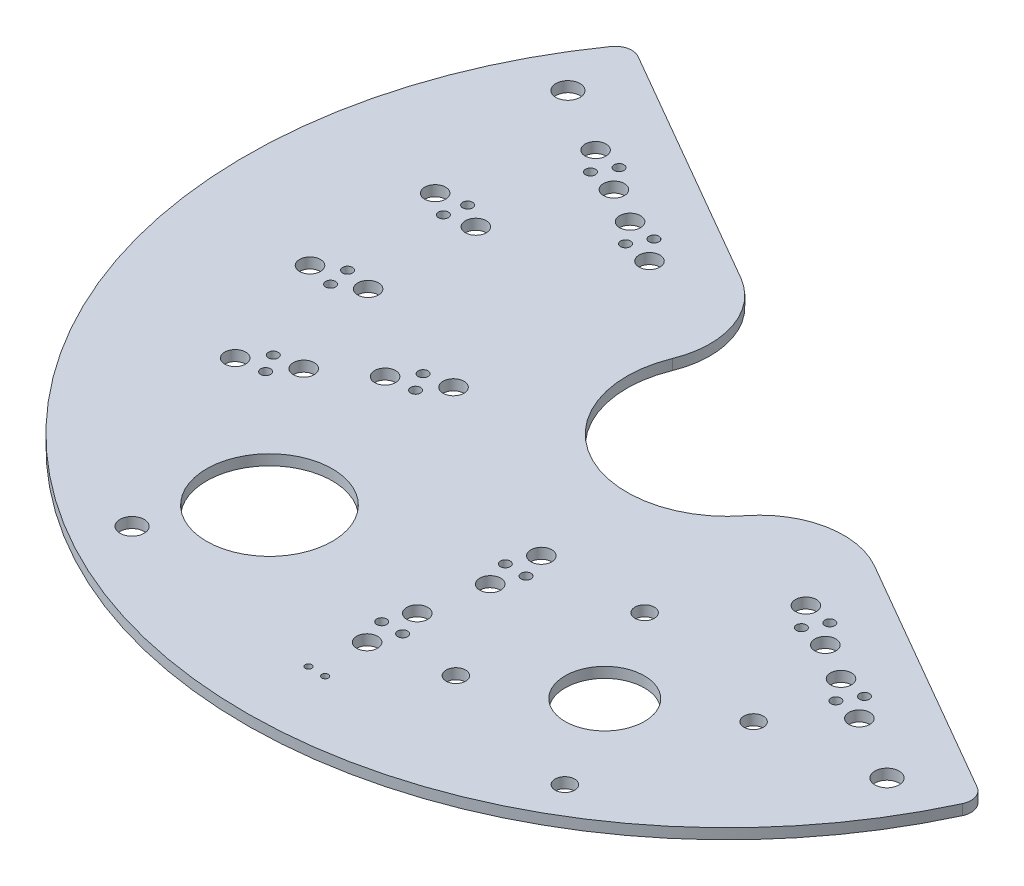
SolidWorks part; units mm, degrees
ref_plane "Front Plane" through (0, 0, 0) normal (0, 0, 1) x (1, 0, 0)
ref_plane "Top Plane" through (0, 0, 0) normal (0, 1, 0) x (1, 0, 0)
ref_plane "Right Plane" through (0, 0, 0) normal (1, 0, 0) x (0, 0, -1)
sketch "Sketch1" plane through (0, 0, 0) normal (0, 1, 0) x (1, 0, 0)
  line L0 (0, 50.8) -> (0, 59.6199) construction
  line L1 (0, 50.8) -> (11.3081, 50.8) construction
  line L2 (0, 0) -> (0, 47) construction
  line L3 (0, 0) -> (-46.286, 8.1615) construction
  line L4 (0, 0) -> (0, 47) construction
  line L5 (0, 0) -> (-46.286, -8.1615) construction
  line L6 (-30.1951, -16.4814) -> (-38.7564, -18.616) construction
  line L7 (1.7716, -33.8648) -> (4.3514, -25.4269) construction
  line L8 (31.2901, -20.38) -> (25.051, -14.141) construction
  line L9 (-31.8057, 17.1605) -> (-38.0448, 23.3996) construction
  circle A0 centre (0, 0) radius 50.8 construction
  circle A1 centre (0, 0) radius 15.24
  circle A2 centre (0, 0) radius 73.025
  circle A3 centre (0, 50.8) radius 6.3 construction
  circle A4 centre (25.4, 43.9941) radius 6.3 construction
  circle A5 centre (43.9941, 25.4) radius 6.3 construction
  circle A6 centre (50.8, 0) radius 6.3 construction
  circle A7 centre (43.9941, -25.4) radius 6.3 construction
  circle A8 centre (25.4, -43.9941) radius 6.3 construction
  circle A9 centre (0, -50.8) radius 6.3 construction
  circle A10 centre (-25.4, -43.9941) radius 6.3 construction
  circle A11 centre (-43.9941, -25.4) radius 6.3 construction
  circle A12 centre (-50.8, 0) radius 6.3 construction
  circle A13 centre (-43.9941, 25.4) radius 6.3 construction
  circle A14 centre (-25.4, 43.9941) radius 6.3 construction
  circle A15 centre (0, 50.8) radius 1.585 construction
  circle A16 centre (-1.585, 50.8) radius 0.75
  circle A17 centre (1.585, 50.8) radius 0.75
  circle A18 centre (0, 50.8) radius 3.8 construction
  circle A19 centre (0, 54.6) radius 1.585
  circle A20 centre (0, 47) radius 1.585
  circle A21 centre (47.285, 27.3) radius 1.585
  circle A22 centre (43.2016, 26.7727) radius 0.75
  circle A23 centre (44.7866, 24.0273) radius 0.75
  circle A24 centre (40.7032, 23.5) radius 1.585
  circle A25 centre (47.285, -27.3) radius 1.585
  circle A26 centre (44.7866, -24.0273) radius 0.75
  circle A27 centre (43.2016, -26.7727) radius 0.75
  circle A28 centre (40.7032, -23.5) radius 1.585
  circle A29 centre (0, -54.6) radius 1.585
  circle A30 centre (1.585, -50.8) radius 0.75
  circle A31 centre (-1.585, -50.8) radius 0.75
  circle A32 centre (0, -47) radius 1.585
  circle A33 centre (-47.285, -27.3) radius 1.585
  circle A34 centre (-43.2016, -26.7727) radius 0.75
  circle A35 centre (-44.7866, -24.0273) radius 0.75
  circle A36 centre (-40.7032, -23.5) radius 1.585
  circle A37 centre (-47.285, 27.3) radius 1.585
  circle A38 centre (-44.7866, 24.0273) radius 0.75
  circle A39 centre (-43.2016, 26.7727) radius 0.75
  circle A40 centre (-40.7032, 23.5) radius 1.585
  circle A41 centre (25.4, 43.9941) radius 20
  circle A42 centre (-25.4, -43.9941) radius 9.525
  circle A43 centre (25.4, -43.9941) radius 6
  circle A44 centre (-46.286, 8.1615) radius 1.585
  circle A45 centre (-50.3035, 7.2604) radius 0.75
  circle A46 centre (-49.753, 10.3822) radius 0.75
  circle A47 centre (-53.7705, 9.4812) radius 1.585
  circle A48 centre (-46.286, -8.1615) radius 1.585
  circle A49 centre (-49.753, -10.3822) radius 0.75
  circle A50 centre (-50.3035, -7.2604) radius 0.75
  circle A51 centre (-53.7705, -9.4812) radius 1.585
  circle A52 centre (-30.191, -16.4817) radius 6.3 construction
  circle A53 centre (-30.191, -16.4817) radius 1.585 construction
  circle A54 centre (-29.3973, -17.8553) radius 0.75
  circle A55 centre (-31.002, -15.1168) radius 0.75
  circle A56 centre (-30.191, -16.4817) radius 3.8 construction
  circle A57 centre (-33.5032, -18.378) radius 1.585
  circle A58 centre (-26.9143, -14.5903) radius 1.585
  circle A59 centre (1.7693, -33.8681) radius 6.3 construction
  circle A60 centre (1.7693, -33.8681) radius 1.585 construction
  circle A61 centre (0.1831, -33.841) radius 0.75
  circle A62 centre (3.3569, -33.8759) radius 0.75
  circle A63 centre (1.7693, -33.8681) radius 3.8 construction
  circle A64 centre (1.8498, -30.0524) radius 1.585
  circle A65 centre (1.7028, -37.651) radius 1.585
  circle A66 centre (31.7545, -18.4007) radius 6.3 construction
  circle A67 centre (31.7545, -18.4007) radius 1.585 construction
  circle A68 centre (30.9859, -19.7885) radius 0.75
  circle A69 centre (32.5067, -17.0026) radius 0.75
  circle A70 centre (31.7545, -18.4007) radius 3.8 construction
  circle A71 centre (28.4231, -16.5382) radius 1.585
  circle A72 centre (35.0633, -20.2353) radius 1.585
  circle A73 centre (-31.9359, 18.6471) radius 6.3 construction
  circle A74 centre (-31.9359, 18.6471) radius 1.585 construction
  circle A75 centre (-32.7045, 17.2593) radius 0.75
  circle A76 centre (-31.1837, 20.0452) radius 0.75
  circle A77 centre (-31.9359, 18.6471) radius 3.8 construction
  circle A78 centre (-35.2672, 20.5095) radius 1.585
  circle A79 centre (-28.627, 16.8125) radius 1.585
  point P50 (0, 0)
  point P84 (0, 0)
  dimension "D1" = 12
  dimension "D2" = 101.6
  dimension "D3" = 3.17
  dimension "D4" = 1.5
  dimension "D5" = 7.6
  dimension "D6" = 6
  dimension "D7" = 3.17
  dimension "D8" = 40
  dimension "D9" = 19.05
  dimension "D10" = 12
  dimension "D11" = 146.05
  dimension "D12" = 30.48
  dimension "D14" = 80
  dimension "D16" = 100
  dimension "D13" = 2
  dimension "D15" = 2
extrude "Boss-Extrude1" add sketch "Sketch1" against normal blind 1.5875
sketch "Sketch2" plane through (0, 0, 0) normal (0, 1, 0) x (1, 0, 0)
  line L0 (0, 0) -> (0, 66.04) construction
  line L1 (0, 0) -> (-57.1923, 33.02) construction
  circle A0 centre (0, 0) radius 66.04 construction
  circle A1 centre (0, 66.04) radius 1.8288 construction
  circle A2 centre (-57.1923, 33.02) radius 1.8288
  circle A3 centre (33.02, 57.1923) radius 1.8288
  circle A4 centre (57.1923, -33.02) radius 1.8288
  circle A5 centre (-33.02, -57.1923) radius 1.8288
  point P17 (0, 0)
  dimension "D1" = 132.08
  dimension "D2" = 3.6576
  dimension "D3" = 2
  dimension "D4" = 60
  dimension "D5" = 4
extrude "Cut-Extrude1" cut sketch "Sketch2" against normal through all
sketch "Sketch3" plane through (0, 0, 0) normal (0, 1, 0) x (1, 0, 0)
  line L0 (-57.1923, 33.02) -> (57.1923, -33.02) construction
  line L1 (-59.5338, 44.6372) -> (68.4238, -29.2392)
  line L2 (-52.7473, 40.719) -> (61.6373, -25.321) construction
  arc A0 (68.4238, -29.2392) -> (-59.5338, 44.6372) centre (0, 0) ccw
  dimension "D1" = 8.89
extrude "Cut-Extrude2" cut sketch "Sketch3" against normal through all
fillet "Fillet1" radius 12.7 2 edges at (15.165, -0.7937, -1.5098) (-6.275, -0.7937, -13.8882)
fillet "Fillet2" radius 2.54 2 edges at (67.2161, -0.7937, 28.542) (-58.3261, -0.7937, -43.9399)
sketch "Sketch4" plane through (0, 0, 0) normal (0, 1, 0) x (1, 0, 0)
  line L0 (0, 0) -> (0, -73.025) construction
  arc A0 (-59.6949, 42.0615) -> (66.2738, -30.6666) centre (0, 0) ccw construction
  circle A1 centre (0, 0) radius 62.23 construction
  circle A2 centre (0, -62.23) radius 0.4953 construction
  circle A3 centre (1.27, -62.23) radius 0.4953
  circle A4 centre (-1.27, -62.23) radius 0.4953
  dimension "D1" = 0.9906
  dimension "D4" = 124.46
  dimension "D2" = 2
  dimension "D3" = 2
extrude "Cut-Extrude3" cut sketch "Sketch4" against normal through all
sketch "Sketch5" plane through (0, -1.5875, 0) normal (0, -1, 0) x (1, 0, 0)
  line L0 (34.4907, 15.2341) -> (45.0238, 21.3018)
  line L1 (-31.0536, -21.3854) -> (-30.5378, -22.2779)
  line L2 (-30.0652, -20.8147) -> (-29.5513, -21.704)
  line L3 (-30.5378, -22.2779) -> (-40.9598, -28.3409)
  line L13 (33.3365, 26.1699) -> (41.5359, 31.0198)
  line L14 (28.0125, 9.134) -> (57.7422, 26.2984)
  line L29 (46.7892, 22.3211) -> (54.7743, 26.9312)
  line L30 (29.0711, 12.1121) -> (33.5009, 14.6639)
  line L31 (6.096, 41.9407) -> (6.096, 51.4811)
  line L32 (32.4795, 23.822) -> (40.9598, 28.3409)
  line L33 (-6.096, 38.6381) -> (-6.096, 51.4811)
  line L34 (4.064, 40.0736) -> (4.064, 49.6426)
  line L35 (-21.9165, -19.6925) -> (-41.5359, -31.0198)
  line L39 (-4.064, 36.8606) -> (-4.064, 49.6426)
  line L40 (-30.4135, 24.5983) -> (-41.5359, 31.0198)
  line L42 (-29.8903, 21.9498) -> (-40.9598, 28.3409)
  line L93 (-25.0455, -19.0828) -> (-29.5513, -21.704)
  arc A0 (1.2946, 63.4357) -> (1.2454, 61.0243) centre (1.27, 62.23) ccw
  arc A1 (-1.1373, 61.0264) -> (-1.1844, 63.4379) centre (-1.27, 62.23) ccw
  arc A2 (-1.1373, 61.0264) -> (-54.0489, -28.3589) centre (0, 0) ccw
  arc A3 (-1.1844, 63.4379) -> (-56.1144, -29.6131) centre (0, 0) ccw
  arc A4 (54.7743, 26.9312) -> (1.2454, 61.0243) centre (0, 0) ccw
  arc A5 (-56.1144, -29.6131) -> (-54.0489, -28.3589) centre (-55.1689, -28.8424) ccw
  arc A6 (6.096, 51.4811) -> (2.3857, 51.7858) centre (0, 0) ccw
  arc A7 (32.4795, 23.822) -> (4.064, 40.0736) centre (0, 0) ccw
  arc A8 (2.3857, 51.7858) -> (2.3071, 49.7553) centre (1.585, 50.8) ccw
  arc A9 (-2.3071, 49.7553) -> (-2.3857, 51.7858) centre (-1.585, 50.8) ccw
  arc A10 (-48.5987, -10.912) -> (-50.5848, -11.342) centre (-49.753, -10.3822) ccw
  arc A11 (-51.4133, -6.6431) -> (-49.4, -6.3679) centre (-50.3035, -7.2604) ccw
  arc A12 (46.0407, 23.8268) -> (44.2429, 22.8796) centre (44.7866, 24.0273) ccw
  arc A13 (41.9358, 26.8756) -> (43.655, 27.959) centre (43.2016, 26.7727) ccw
  arc A14 (-49.4, 6.3679) -> (-51.4133, 6.6431) centre (-50.3035, 7.2604) ccw
  arc A15 (-50.5848, 11.342) -> (-48.5987, 10.912) centre (-49.753, 10.3822) ccw
  arc A16 (57.7422, 26.2984) -> (1.2946, 63.4357) centre (0, 0) ccw
  arc A17 (-2.3857, 51.7858) -> (-6.096, 51.4811) centre (0, 0) ccw
  arc A18 (-2.3071, 49.7553) -> (-4.064, 49.6426) centre (0, 0) ccw
  arc A19 (45.0238, 21.3018) -> (44.2429, 22.8796) centre (0, 0) ccw
  arc A20 (29.0711, 12.1121) -> (-25.0455, -19.0828) centre (2.3366, -4.0471) ccw
  arc A21 (28.0125, 9.134) -> (-21.9165, -19.6925) centre (2.3859, -4.1326) ccw
  arc A22 (46.7892, 22.3211) -> (46.0407, 23.8268) centre (0, 0) ccw
  arc A23 (43.655, 27.959) -> (41.5359, 31.0198) centre (0, 0) ccw
  arc A24 (-46.0407, -23.8268) -> (-44.2429, -22.8796) centre (-44.7866, -24.0273) ccw
  arc A25 (-41.9358, -26.8756) -> (-43.655, -27.959) centre (-43.2016, -26.7727) ccw
  arc A26 (41.9358, 26.8756) -> (40.9598, 28.3409) centre (0, 0) ccw
  circle A27 centre (1.27, 62.23) radius 0.4953
  arc A28 (-43.655, 27.959) -> (-41.9358, 26.8756) centre (-43.2016, 26.7727) ccw
  arc A29 (-44.2429, 22.8796) -> (-46.0407, 23.8268) centre (-44.7866, 24.0273) ccw
  circle A30 centre (-1.27, 62.23) radius 0.4953
  arc A31 (-43.655, -27.959) -> (-41.5359, -31.0198) centre (0, 0) ccw
  circle A32 centre (-26.7727, 43.2016) radius 1.27 [skipped]
  circle A33 centre (-24.0273, 44.7866) radius 1.27 [skipped]
  circle A34 centre (24.0273, 44.7866) radius 1.27 [skipped]
  circle A35 centre (26.7727, 43.2016) radius 1.27 [skipped]
  circle A36 centre (50.8, 1.585) radius 1.27 [skipped]
  circle A37 centre (50.8, -1.585) radius 1.27 [skipped]
  circle A38 centre (44.7866, -24.0273) radius 1.27 [skipped]
  circle A39 centre (43.2016, -26.7727) radius 1.27 [skipped]
  circle A40 centre (26.7727, -43.2016) radius 1.27 [skipped]
  circle A41 centre (24.0273, -44.7866) radius 1.27 [skipped]
  circle A42 centre (1.585, -50.8) radius 1.27 [skipped]
  circle A43 centre (-1.585, -50.8) radius 1.27 [skipped]
  circle A44 centre (-24.0273, -44.7866) radius 1.27 [skipped]
  circle A45 centre (-26.7727, -43.2016) radius 1.27 [skipped]
  circle A46 centre (-50.8, 1.585) radius 1.27 [skipped]
  circle A47 centre (-50.8, -1.585) radius 1.27 [skipped]
  arc A48 (-41.9358, -26.8756) -> (-40.9598, -28.3409) centre (0, 0) ccw
  arc A49 (-40.9598, 28.3409) -> (-41.9358, 26.8756) centre (0, 0) ccw
  arc A50 (33.3365, 26.1699) -> (6.096, 41.9407) centre (0, 0) ccw
  circle A51 centre (1.585, 50.8) radius 0.75
  arc A52 (-46.0407, 23.8268) -> (-47.6319, 20.4612) centre (0, 0) ccw
  arc A53 (4.064, 49.6426) -> (2.3071, 49.7553) centre (0, 0) ccw
  arc A54 (-41.5359, 31.0198) -> (-43.655, 27.959) centre (0, 0) ccw
  arc A55 (-6.096, 38.6381) -> (-30.4135, 24.5983) centre (0, 0) ccw
  arc A56 (-4.064, 36.8606) -> (-29.8903, 21.9498) centre (0, 0) ccw
  arc A57 (-44.2429, 22.8796) -> (-48.5987, 10.912) centre (0, 0) ccw
  circle A58 centre (-1.585, 50.8) radius 0.75
  circle A59 centre (43.2016, 26.7727) radius 0.75
  arc A60 (-47.6319, 20.4612) -> (-50.5848, 11.342) centre (0, 0) ccw
  arc A61 (-51.4133, 6.6431) -> (-51.4133, -6.6431) centre (0, 0) ccw
  arc A62 (-49.4, 6.3679) -> (-49.4, -6.3679) centre (0, 0) ccw
  circle A63 centre (44.7866, 24.0273) radius 0.75
  arc A64 (-50.5848, -11.342) -> (-46.0407, -23.8268) centre (0, 0) ccw
  arc A65 (-48.5987, -10.912) -> (-44.2429, -22.8796) centre (0, 0) ccw
  circle A66 centre (-43.2016, 26.7727) radius 0.75
  circle A67 centre (-44.7866, 24.0273) radius 0.75
  circle A68 centre (-49.753, 10.3822) radius 0.75
  circle A69 centre (-50.3035, 7.2604) radius 0.75
  circle A70 centre (-50.3035, -7.2604) radius 0.75
  circle A71 centre (-49.753, -10.3822) radius 0.75
  circle A72 centre (-44.7866, -24.0273) radius 0.75
  circle A73 centre (-43.2016, -26.7727) radius 0.75
  arc A74 (29.7503, 20.2948) -> (30.8424, 21.1896) centre (30.9918, 19.8934) ccw
  arc A75 (4.5236, 34.6192) -> (30.8424, 21.1896) centre (5.7054, 4.4312) cw
  arc A76 (4.4841, 33.194) -> (29.7503, 20.2948) centre (4.8534, 2.7227) cw
  arc A77 (33.7473, 16.7292) -> (32.8413, 15.8053) centre (32.514, 17.0324) ccw
  arc A78 (33.5009, 14.6639) -> (32.8413, 15.8053) centre (-9.9501, -9.686) ccw
  arc A79 (34.4907, 15.2341) -> (33.7473, 16.7292) centre (-12.2934, -7.0976) ccw
  arc A80 (-0.8928, 32.9745) -> (-0.4432, 34.9562) centre (0.075, 33.7967) ccw
  arc A81 (-29.697, 19.0828) -> (-0.4432, 34.9562) centre (2.1808, -4.7732) cw
  arc A82 (4.5236, 34.6192) -> (4.4841, 33.194) centre (3.4532, 33.9357) ccw
  arc A84 (-29.697, 19.0828) -> (-28.1584, 17.7555) centre (-29.4254, 17.8422) ccw
  arc A85 (-28.1584, 17.7555) -> (-0.8928, 32.9745) centre (0.881, -2.2367) cw
  arc A86 (-31.3368, 13.0383) -> (-32.985, 14.2011) centre (-31.3367, 14.7878) ccw
  arc A87 (-32.985, 14.2011) -> (-34.3304, 11.6344) centre (112.8254, -63.8668) ccw
  arc A88 (-33.9153, -16.8172) -> (-31.9293, -16.3872) centre (-32.7611, -17.3469) ccw
  arc A89 (-31.9293, -16.3872) -> (-32.6415, -14.9048) centre (-79.0072, -38.0929) ccw
  arc A90 (-30.0652, -20.8147) -> (-31.0536, -21.3854) centre (-31.1268, -20.1175) ccw
  arc A92 (-34.3304, 11.6344) -> (-33.9153, -16.8172) centre (-7.3644, -2.2011) ccw
  arc A93 (-31.3368, 13.0383) -> (-32.6415, -14.9048) centre (-7.0347, -2.0984) ccw
  point P62 (0, 0)
  point P64 (0, 0)
  point P65 (-31.3172, -21.5437)
  point P67 (0, 0)
  point P86 (0, 0)
  point P96 (-30.0652, -20.8147)
  point P99 (0, 0)
  point P101 (-31.0536, -21.3854)
  point P102 (-30.5299, -22.2915)
  point P105 (0, 0)
  point P106 (-29.5513, -21.704)
  dimension "D13" = 12
  dimension "D15" = 3
extrude "Boss-Extrude2" add sketch "Sketch5" along normal blind 0.1016
sketch "Sketch6" plane through (0, -1.5875, 0) normal (0, -1, 0) x (1, 0, 0)
  line L0 (0, 0) -> (25.4, 43.9941) construction
  line L1 (25.4, 43.9941) -> (36.5125, 63.2415) construction
  circle A0 centre (25.4, 43.9941) radius 16.51 construction
  arc A1 (66.2738, 30.6666) -> (-59.6949, -42.0615) centre (0, 0) ccw construction
  circle A2 centre (33.655, 58.2922) radius 1.4732
  circle A3 centre (11.1019, 52.2491) radius 1.4732
  circle A4 centre (17.145, 29.696) radius 1.4732
  circle A5 centre (39.6981, 35.7391) radius 1.4732
  point P20 (25.4, 43.9941)
  dimension "D1" = 2.9464
extrude "Cut-Extrude4" cut sketch "Sketch6" against normal through all
